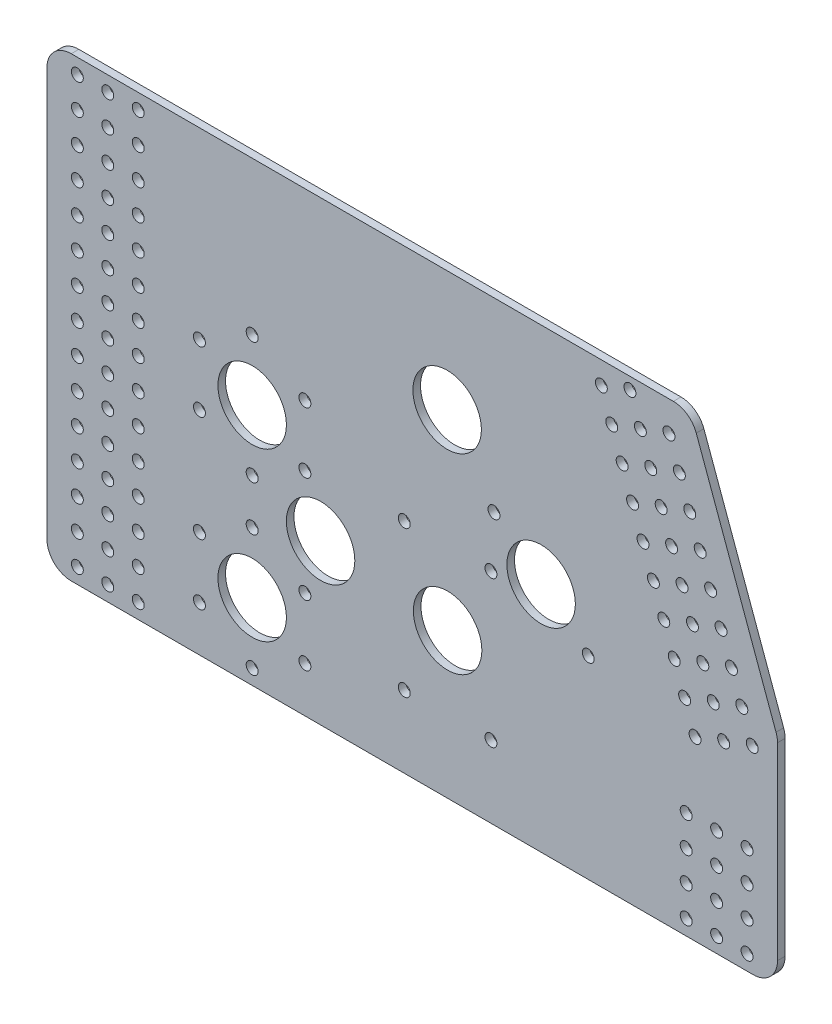
SolidWorks part; units mm, degrees
ref_plane "Front Plane" through (0, 0, 0) normal (0, 0, 1) x (1, 0, 0)
ref_plane "Top Plane" through (0, 0, 0) normal (0, 1, 0) x (1, 0, 0)
ref_plane "Right Plane" through (0, 0, 0) normal (1, 0, 0) x (0, 0, -1)
sketch "Sketch6" plane through (0, 0, 0) normal (0, 0, 1) x (1, 0, 0)
  line L0 (-62.0347, 275.0603) -> (206.4353, 275.0603)
  line L3 (206.4353, 275.0603) -> (242.7653, 175.2445)
  line L4 (242.7653, 175.2445) -> (242.7653, 84.5603)
  line L6 (242.7653, 84.5603) -> (-62.0347, 84.5603)
  line L7 (-62.0347, 84.5603) -> (-62.0347, 275.0603)
  line L8 (-49.3347, 268.7103) -> (-36.6347, 268.7103) construction
  line L9 (-49.3347, 268.7103) -> (-49.3347, 256.0103) construction
  line L10 (105.1393, -854.8604) -> (105.1393, 49145.1396) construction
  line L11 (169.2687, 265.7779) -> (173.6123, 253.8438) construction
  line L12 (204.6653, 129.0103) -> (204.6653, 116.3103) construction
  line L13 (23.6016, 116.2566) -> (23.6016, 141.6566) construction
  line L14 (23.6016, 185.8526) -> (23.6016, 211.2526) construction
  line L15 (-894.8607, 145.1396) -> (49105.1393, 145.1396) construction
  circle A0 centre (123.2241, 114.6088) radius 2.4892
  circle A1 centre (87.0545, 114.6088) radius 2.4892
  circle A2 centre (-49.3347, 268.7103) radius 2.4892
  circle A3 centre (-49.3347, 90.9103) radius 2.4892
  circle A4 centre (-36.6347, 268.7103) radius 2.4892
  circle A5 centre (-23.9347, 268.7103) radius 2.4892
  circle A6 centre (-36.6347, 256.0103) radius 2.4892
  circle A7 centre (-23.9347, 256.0103) radius 2.4892
  circle A8 centre (-36.6347, 243.3103) radius 2.4892
  circle A9 centre (-23.9347, 243.3103) radius 2.4892
  circle A10 centre (-36.6347, 230.6103) radius 2.4892
  circle A11 centre (-23.9347, 230.6103) radius 2.4892
  circle A12 centre (-36.6347, 217.9103) radius 2.4892
  circle A13 centre (-23.9347, 217.9103) radius 2.4892
  circle A14 centre (-36.6347, 205.2103) radius 2.4892
  circle A15 centre (-23.9347, 205.2103) radius 2.4892
  circle A16 centre (-36.6347, 192.5103) radius 2.4892
  circle A17 centre (-23.9347, 192.5103) radius 2.4892
  circle A18 centre (-36.6347, 179.8103) radius 2.4892
  circle A19 centre (-23.9347, 179.8103) radius 2.4892
  circle A20 centre (-36.6347, 167.1103) radius 2.4892
  circle A21 centre (-23.9347, 167.1103) radius 2.4892
  circle A22 centre (-36.6347, 154.4103) radius 2.4892
  circle A23 centre (-23.9347, 154.4103) radius 2.4892
  circle A24 centre (-36.6347, 141.7103) radius 2.4892
  circle A25 centre (-23.9347, 141.7103) radius 2.4892
  circle A26 centre (-36.6347, 129.0103) radius 2.4892
  circle A27 centre (-23.9347, 129.0103) radius 2.4892
  circle A28 centre (-36.6347, 116.3103) radius 2.4892
  circle A29 centre (-23.9347, 116.3103) radius 2.4892
  circle A30 centre (-36.6347, 103.6103) radius 2.4892
  circle A31 centre (-23.9347, 103.6103) radius 2.4892
  circle A32 centre (-36.6347, 90.9103) radius 2.4892
  circle A33 centre (-23.9347, 90.9103) radius 2.4892
  circle A34 centre (-49.3347, 256.0103) radius 2.4892
  circle A35 centre (-49.3347, 243.3103) radius 2.4892
  circle A36 centre (-49.3347, 230.6103) radius 2.4892
  circle A37 centre (-49.3347, 217.9103) radius 2.4892
  circle A38 centre (-49.3347, 205.2103) radius 2.4892
  circle A39 centre (-49.3347, 192.5103) radius 2.4892
  circle A40 centre (-49.3347, 179.8103) radius 2.4892
  circle A41 centre (-49.3347, 167.1103) radius 2.4892
  circle A42 centre (-49.3347, 154.4103) radius 2.4892
  circle A43 centre (-49.3347, 141.7103) radius 2.4892
  circle A44 centre (-49.3347, 129.0103) radius 2.4892
  circle A45 centre (-49.3347, 116.3103) radius 2.4892
  circle A46 centre (-49.3347, 103.6103) radius 2.4892
  circle A47 centre (-49.3347, 90.9103) radius 2.4892
  circle A48 centre (169.2687, 265.7779) radius 2.4892
  circle A49 centre (181.2028, 270.1215) radius 2.4892
  circle A50 centre (197.4805, 262.5311) radius 2.4892
  circle A51 centre (173.6123, 253.8438) radius 2.4892
  circle A52 centre (185.5464, 258.1874) radius 2.4892
  circle A53 centre (201.8242, 250.597) radius 2.4892
  circle A54 centre (177.956, 241.9097) radius 2.4892
  circle A55 centre (189.8901, 246.2533) radius 2.4892
  circle A56 centre (206.1678, 238.6629) radius 2.4892
  circle A57 centre (182.2996, 229.9756) radius 2.4892
  circle A58 centre (194.2337, 234.3192) radius 2.4892
  circle A59 centre (210.5115, 226.7288) radius 2.4892
  circle A60 centre (186.6433, 218.0415) radius 2.4892
  circle A61 centre (198.5774, 222.3851) radius 2.4892
  circle A62 centre (214.8551, 214.7947) radius 2.4892
  circle A63 centre (190.9869, 206.1074) radius 2.4892
  circle A64 centre (202.921, 210.451) radius 2.4892
  circle A65 centre (219.1988, 202.8606) radius 2.4892
  circle A66 centre (195.3306, 194.1733) radius 2.4892
  circle A67 centre (207.2647, 198.5169) radius 2.4892
  circle A68 centre (223.5424, 190.9265) radius 2.4892
  circle A69 centre (199.6743, 182.2392) radius 2.4892
  circle A70 centre (211.6083, 186.5828) radius 2.4892
  circle A71 centre (227.8861, 178.9924) radius 2.4892
  circle A72 centre (204.0179, 170.3051) radius 2.4892
  circle A73 centre (215.952, 174.6488) radius 2.4892
  circle A74 centre (232.2298, 167.0583) radius 2.4892
  circle A75 centre (208.3616, 158.371) radius 2.4892
  circle A76 centre (220.2957, 162.7147) radius 2.4892
  circle A78 centre (236.5734, 155.1242) radius 2.4892 [skipped]
  circle A79 centre (204.6653, 129.0103) radius 2.4892
  circle A80 centre (217.3653, 129.0103) radius 2.4892
  circle A81 centre (230.0653, 129.0103) radius 2.4892
  circle A82 centre (204.6653, 116.3103) radius 2.4892
  circle A83 centre (217.3653, 116.3103) radius 2.4892
  circle A84 centre (230.0653, 116.3103) radius 2.4892
  circle A85 centre (204.6653, 103.6103) radius 2.4892
  circle A86 centre (217.3653, 103.6103) radius 2.4892
  circle A87 centre (230.0653, 103.6103) radius 2.4892
  circle A88 centre (204.6653, 90.9103) radius 2.4892
  circle A89 centre (217.3653, 90.9103) radius 2.4892
  circle A90 centre (230.0653, 90.9103) radius 2.4892
  circle A91 centre (23.6016, 185.8526) radius 14.2875
  circle A92 centre (52.1422, 151.0564) radius 14.2875
  circle A93 centre (23.6016, 116.2566) radius 14.2875
  circle A94 centre (105.1393, 145.1396) radius 14.2875
  circle A95 centre (104.9447, 224.8273) radius 14.2875
  circle A96 centre (144.1424, 181.3926) radius 14.2875
  circle A100 centre (23.6016, 141.6566) radius 2.4892
  circle A101 centre (45.5987, 128.9566) radius 2.4892
  circle A102 centre (45.5987, 103.5566) radius 2.4892
  circle A103 centre (23.6016, 90.8566) radius 2.4892
  circle A104 centre (1.6046, 103.5566) radius 2.4892
  circle A105 centre (1.6046, 128.9566) radius 2.4892
  circle A106 centre (23.6016, 211.2526) radius 2.4892
  circle A107 centre (45.5987, 198.5526) radius 2.4892
  circle A108 centre (45.5987, 173.1526) radius 2.4892
  circle A109 centre (23.6016, 160.4526) radius 2.4892
  circle A110 centre (1.6046, 173.1526) radius 2.4892
  circle A111 centre (1.6046, 198.5526) radius 2.4892
  circle A112 centre (123.2241, 175.6704) radius 2.4892
  circle A113 centre (87.0545, 175.6704) radius 2.4892
  circle A114 centre (124.4816, 197.5761) radius 2.4892
  circle A115 centre (163.8041, 165.4143) radius 2.4892
  dimension "D1" = 4.9784
  dimension "D2" = 6.35
  dimension "D3" = 4.9784
  dimension "D10" = 4.9784
  dimension "D11" = 4.9784
  dimension "D12" = 4.9784
  dimension "D15" = 4.9784
  dimension "D16" = 4.9784
  dimension "D17" = 4.9784
  dimension "D20" = 4.9784
  dimension "D21" = 28.575
  dimension "D22" = 28.575
  dimension "D23" = 28.575
  dimension "D24" = 28.575
  dimension "D25" = 28.575
  dimension "D26" = 28.575
  dimension "D27" = 4.9784
  dimension "D28" = 4.9784
  dimension "D32" = 4.9784
  dimension "D35" = 4.9784
  dimension "D4" = 12.7
  dimension "D5" = 3
  dimension "D7" = 12.7
  dimension "D8" = 12.7
  dimension "D9" = 6.35
  dimension "D14" = 12.7
  dimension "D19" = 12.7
  dimension "D29" = 25.4
  dimension "D31" = 25.4
  dimension "D33" = 6
  dimension "D34" = 25.4
  dimension "D36" = 18.0848
  dimension "D37" = 30.5308
  dimension "D6" = 15
  dimension "D13" = 10
  dimension "D18" = 4
  dimension "D30" = 6
extrude "Boss-Extrude1" add sketch "Sketch6" along normal blind 3.175
fillet "Fillet1" radius 10.16 5 edges at (242.7653, 84.5603, 1.5875) (242.7653, 175.2445, 1.5875) (206.4353, 275.0603, 1.5875) (-62.0347, 84.5603, 1.5875) (-62.0347, 275.0603, 1.5875)
